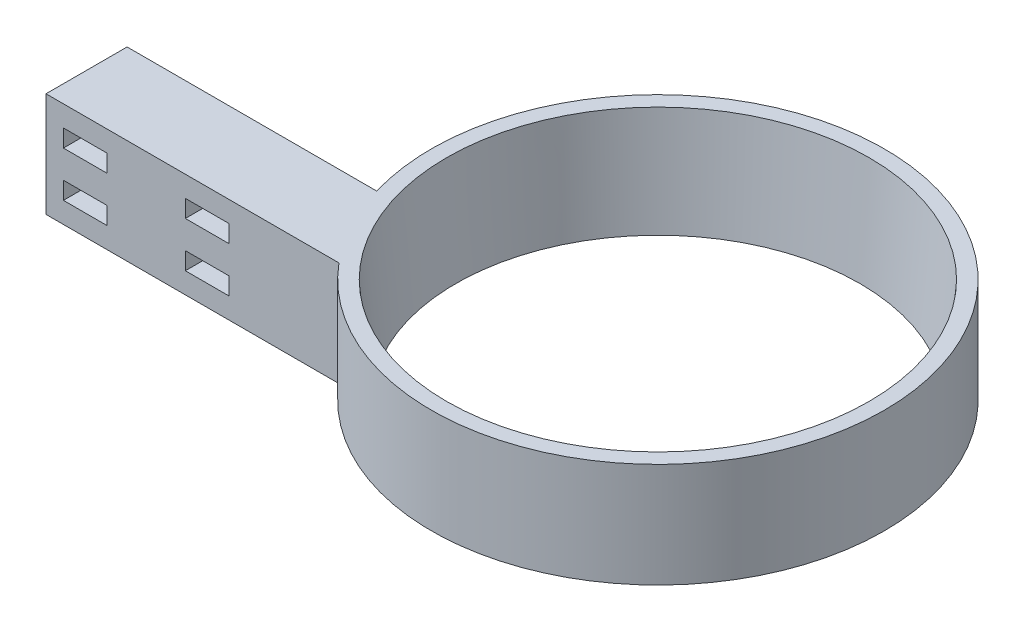
SolidWorks part; units mm, degrees
ref_plane "Front Plane" through (0, 0, 0) normal (0, 0, 1) x (1, 0, 0)
ref_plane "Top Plane" through (0, 0, 0) normal (0, 1, 0) x (1, 0, 0)
ref_plane "Right Plane" through (0, 0, 0) normal (1, 0, 0) x (0, 0, -1)
sketch "Sketch1" plane through (0, 0, 0) normal (0, 1, 0) x (1, 0, 0)
  line L0 (0, 0) -> (-41.275, 0) construction
  circle A0 centre (0, 0) radius 41.275
  dimension "D1" = 82.55
extrude "Outer Circle" add sketch "Sketch1" along normal blind 19.05 contours A0
ref_plane "Connector Midplane" through (0, 0, 19.05) normal (0, 0, 1) x (1, 0, 0)
sketch "Sketch3" plane through (0, 0, 0) normal (0, -1, 0) x (1, 0, 0)
  line L0 (0, 0) -> (-41.275, 0) construction
  line L1 (-31.6935, 26.4414) -> (-85.09, 26.4414)
  line L2 (-85.09, 26.4414) -> (-85.09, 11.6586)
  line L3 (-85.09, 11.6586) -> (-39.5942, 11.6586)
  line L4 (10.4775, 19.05) -> (-10.4775, 19.05) construction
  circle A0 centre (0, 0) radius 41.275 construction
  arc A1 (-39.5942, 11.6586) -> (-31.6935, 26.4414) centre (0, 0) cw
  point P7 (-85.09, 19.05)
  dimension "D1" = 14.7828
  dimension "D2" = 43.815
extrude "Connector" add sketch "Sketch3" against normal blind 3.175 contours L3 A1 L1 L2
sketch "Sketch4" plane through (0, 0, 26.4414) normal (0, 0, 1) x (1, 0, 0)
  line L0 (-85.09, 3.175) -> (-85.09, 19.05)
  line L1 (-85.09, 19.05) -> (-31.6935, 19.05)
  line L2 (41.275, 19.05) -> (-41.275, 19.05) construction
  line L3 (-31.6935, 19.05) -> (-31.6935, 3.175)
  line L4 (-31.6935, 3.175) -> (-85.09, 3.175) construction
  line L5 (-31.6935, 3.175) -> (-85.09, 3.175)
  line L6 (-31.6935, 3.175) -> (-39.5942, 3.175) construction
  line L7 (-31.6935, 3.175) -> (-31.6935, 0) construction
sketch "Sketch5" plane through (0, 0, 11.6586) normal (0, 0, -1) x (-1, 0, 0)
  line L0 (85.09, 3.175) -> (85.09, 19.05)
  line L1 (85.09, 19.05) -> (31.6935, 19.05)
  line L2 (31.6935, 19.05) -> (31.6935, 3.175)
  line L3 (31.6935, 3.175) -> (85.09, 3.175)
  line L4 (41.275, 19.05) -> (-41.275, 19.05) construction
extrude "Outside Wall" add sketch "Sketch4" against normal blind 3.175
extrude "Inside Wall" add sketch "Sketch5" against normal up to surface (11.6078 mm away) up to face at (-59.5913, 11.1125, 23.2664)
sketch "Sketch2" plane through (0, 0, 0) normal (0, -1, 0) x (1, 0, 0)
  circle A0 centre (0, 0) radius 36.83
  dimension "D1" = 73.66
extrude "Cup Cut" cut sketch "Sketch2" against normal through all draft 5 draft outward yes
sketch "Sketch7" plane through (0, 0, 26.4414) normal (0, 0, 1) x (1, 0, 0)
  line L0 (-85.09, 9.525) -> (-31.6935, 9.525) construction
  line L1 (-85.09, 19.05) -> (-85.09, 0) construction
  line L2 (-31.6935, 19.05) -> (-31.6935, 0) construction
  line L4 (-31.6935, 19.05) -> (-85.09, 19.05) construction
  line L7 (-81.915, 15.24) -> (-73.9775, 15.24)
  line L8 (-81.915, 15.24) -> (-81.915, 12.065)
  line L9 (-81.915, 12.065) -> (-73.9775, 12.065)
  line L10 (-73.9775, 15.24) -> (-73.9775, 12.065)
  line L11 (-81.915, 15.24) -> (-73.9775, 12.065) construction
  line L12 (-81.915, 12.065) -> (-73.9775, 15.24) construction
  point P12 (-77.9462, 13.6525)
  dimension "D1" = 3.175
  dimension "D2" = 7.9375
  dimension "D3" = 9.525
  dimension "D4" = 3.81
  dimension "D5" = 3.175
extrude "Slot" cut sketch "Sketch7" against normal up to next
ref_plane "Plane2" through (0, 9.525, 0) normal (0, 1, 0) x (1, 0, 0)
pattern_linear "LPattern1" count 2 spacing 22.225 along (1, 0, 0) of "Slot"
mirror "Mirror2" about plane through (0, 9.525, 0) normal (0, 1, 0) of "LPattern1"
sketch "Sketch6" plane through (0, 19.05, 0) normal (0, 1, 0) x (1, 0, 0)
  line L0 (-85.09, -11.6586) -> (-85.09, -26.4414) construction
  line L1 (-85.09, -20.5486) -> (-78.74, -20.5486)
  line L2 (-85.09, -20.5486) -> (-85.09, -17.5514)
  line L3 (-85.09, -17.5514) -> (-78.74, -17.5514)
  line L4 (-78.74, -20.5486) -> (-78.74, -17.5514)
  line L5 (-72.39, -20.5486) -> (-72.39, -17.5514)
  line L6 (-72.39, -20.5486) -> (-66.04, -20.5486)
  line L7 (-66.04, -20.5486) -> (-66.04, -17.5514)
  line L8 (-72.39, -17.5514) -> (-66.04, -17.5514)
  line L9 (-59.69, -20.5486) -> (-59.69, -17.5514)
  line L10 (-59.69, -20.5486) -> (-53.34, -20.5486)
  line L11 (-53.34, -20.5486) -> (-53.34, -17.5514)
  line L12 (-59.69, -17.5514) -> (-53.34, -17.5514)
  line L13 (-10.4775, -19.05) -> (10.4775, -19.05) construction
  line L14 (-59.69, -17.5514) -> (-53.34, -17.5514)
  line L15 (-53.34, -17.5514) -> (-53.34, -20.5486)
  line L16 (-59.69, -20.5486) -> (-53.34, -20.5486)
  line L17 (-59.69, -17.5514) -> (-59.69, -20.5486)
  line L18 (-72.39, -17.5514) -> (-66.04, -17.5514)
  line L19 (-66.04, -17.5514) -> (-66.04, -20.5486)
  line L20 (-72.39, -20.5486) -> (-66.04, -20.5486)
  line L21 (-72.39, -17.5514) -> (-72.39, -20.5486)
  line L22 (-85.09, -20.5486) -> (-78.74, -20.5486)
  line L23 (-78.74, -17.5514) -> (-78.74, -20.5486)
  line L24 (-85.09, -17.5514) -> (-78.74, -17.5514)
  line L25 (-85.09, -17.5514) -> (-85.09, -20.5486)
  point P6 (-85.09, -19.05)
  point P7 (-85.09, -19.05)
  dimension "D1" = 2.9972
  dimension "D2" = 6.35
  dimension "D3" = 3
  dimension "D4" = 6.35
extrude "Boss-Extrude5" add sketch "Sketch6" along normal blind 3.429 rebuild error yes
fillet "Fillet1" radius 0.508 rebuild error yes
mirror "Mirror1" about plane through (0, 9.525, 0) normal (0, 1, 0) rebuild error yes
ref_plane "Plane3" through (0, 0, -50.8) normal (0, 0, 1) x (1, 0, 0)
